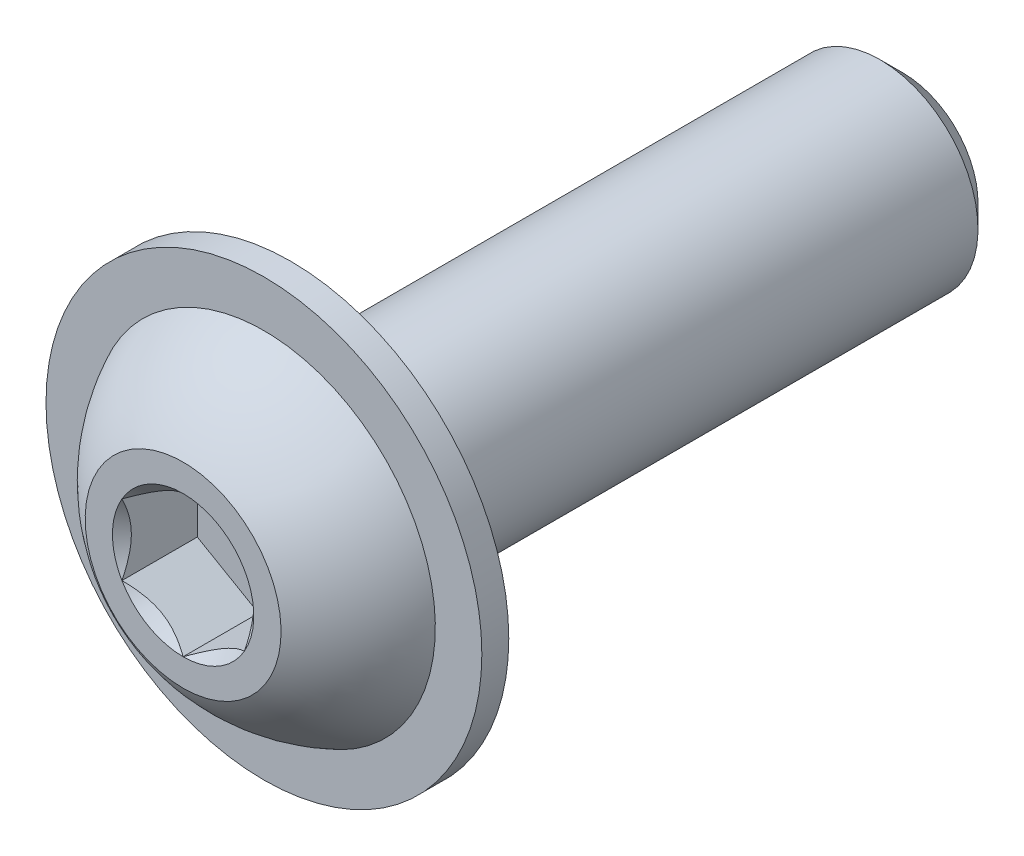
SolidWorks part; units mm, degrees
material "AISI 304"
ref_plane "Front" through (0, 0, 0) normal (0, 0, 1) x (1, 0, 0)
ref_plane "Top" through (0, 0, 0) normal (0, 1, 0) x (1, 0, 0)
ref_plane "Right" through (0, 0, 0) normal (1, 0, 0) x (0, 0, -1)
sketch "Sketch1" plane through (0, 0, 0) normal (1, 0, 0) x (0, 0, -1)
  line L2 (4.4, 4) -> (29.4, 4)
  line L3 (29.4, 4) -> (29.4, 0)
  line L4 (29.4, 0) -> (4.4, 0)
  line L6 (3.3, 7) -> (4.4, 7) construction
  line L7 (29.4, 4) -> (29.4, -4) construction
  line L8 (0, 0) -> (4.4, 0) construction
  line L9 (4.4, 7) -> (4.4, -7) construction
  line L11 (4.4, 4) -> (4.4, 0)
  line L13 (0, 2.5) -> (0, -2.5) construction
  line L14 (0, 2.5) -> (0, 4) construction
  line L15 (3.3, 7) -> (3.3, 8.9) construction
  line L16 (3.3, 8.9) -> (4.4, 8.9) construction
  line L17 (4.4, 8.9) -> (4.4, 7) construction
  line L18 (4.4, 8.9) -> (4.4, -8.9) construction
  arc A3 (0, 4) -> (3.3, 7) centre (6.65, 0) cw construction
  dimension "D1" = 1.1
revolve "Revolve1" add sketch "Sketch1" angle 360 mid plane about L4
sketch "Sketch3" plane through (0, 0, -29.4) normal (0, 0, -1) x (-1, 0, 0)
  circle A0 centre (0, 0) radius 4
curve "Helix/Spiral1" pitch 1.25 height 26.25 turns 21
sketch "Sketch2" plane through (0, 0, 0) normal (1, 0, 0) x (0, 0, -1)
  line L0 (29.4, 4) -> (30.4937, 4)
  line L1 (30.4937, 4) -> (30.025, 3.1881)
  line L2 (30.025, 3.1881) -> (29.8687, 3.1881)
  line L3 (29.8687, 3.1881) -> (29.4, 4)
  line L4 (29.6344, 3.5941) -> (30.2594, 3.5941) construction
  dimension "D1" = 60
  dimension "D2" = 0.1562
  dimension "D3" = 0.625
chamfer "Chamfer1" distance 0.9375 angle 45 1 edges at (0, 4, -29.4)
sweep "Cut-Sweep1" [suppressed] cut profiles "Sketch2" path "Helix/Spiral1"
sketch "Sketch7" plane through (0, 0, 0) normal (1, 0, 0) x (0, 0, -1)
  line L6 (3.3, 7) -> (4.4, 7) construction
  line L8 (0, 0) -> (4.4, 0) construction
  line L11 (4.4, 7) -> (4.4, -7) construction
  line L12 (3.3, 7) -> (4.4, 7)
  line L13 (0, 0) -> (4.4, 0)
  line L14 (0, 2.5) -> (0, -2.5) construction
  line L15 (4.4, 7) -> (4.4, 0)
  line L16 (0, 4) -> (0, 0)
  arc A2 (3.3, 7) -> (0, 4) centre (6.65, 0) ccw construction
  arc A3 (3.3, 7) -> (0, 4) centre (6.65, 0) ccw
revolve "Revolve2" add sketch "Sketch7" angle 360 mid plane about L13
sketch "Sketch11" plane through (0, 0, -4.4) normal (0, 0, -1) x (-1, 0, 0)
  circle A0 centre (0, 0) radius 8.9
extrude "Boss-Extrude3" add sketch "Sketch11" against normal up to vertex (1.1 mm away) up to point (0, 7, -3.3)
sketch "Sketch5" plane through (0, 0, 0) normal (0, 0, 1) x (1, 0, 0)
  line L1 (2.5, -1.4434) -> (2.5, 1.4434)
  line L2 (2.5, 1.4434) -> (0, 2.8868)
  line L3 (0, 2.8868) -> (-2.5, 1.4434)
  line L4 (-2.5, 1.4434) -> (-2.5, -1.4434)
  line L5 (-2.5, -1.4434) -> (0, -2.8868)
  line L6 (0, -2.8868) -> (2.5, -1.4434)
  circle A0 centre (0, 0) radius 2.5 construction
extrude "Cut-Extrude2" cut sketch "Sketch5" against normal blind 3.08
sketch "Sketch6" plane through (0, 0, 0) normal (0, 0, 1) x (1, 0, 0)
  circle A0 centre (0, 0) radius 2.8868
extrude "Cut-Extrude3" cut sketch "Sketch6" against normal blind 3.08 draft 45
sketch "Sketch9" [suppressed] plane through (0, 0, -5.0546) normal (0, 0, 1) x (1, 0, 0)
  circle A2 centre (0, 0) radius 4.7625
extrude "Boss-Extrude2" [suppressed] add sketch "Sketch9" against normal offset from surface (6.35 mm away) 31.75 up to face at (0, 3.0625, -29.4)
sketch "Sketch10" plane through (0, 0, 0) normal (1, 0, 0) x (0, 0, -1)
  line L0 (29.4, 4) -> (29.4, -4) construction
  point P0 (27.525, -4)
  dimension "D1" = 1.875
equation "\"D3@Helix/Spiral1\" = \"Lg@Sketch1\" + \"D4@Helix/Spiral1\""
equation "\"D2@Sketch2\" = \"D4@Helix/Spiral1\" * .125"
equation "\"D3@Sketch2\" = \"D4@Helix/Spiral1\" * .5"
equation "\"D1@Chamfer1\" = \"D4@Helix/Spiral1\" * .75"
equation "\"D1@Cut-Extrude2\" = \"Head Ht@Sketch1\" * .7"
equation "\"D1@Sketch1\" = \"Head Ht@Sketch1\" * .25"
equation "\"D1@Sketch10\" = \"D4@Helix/Spiral1\" * 1.5"
equation "\"D1@Cut-Extrude3\" = \"D1@Cut-Extrude2\""
